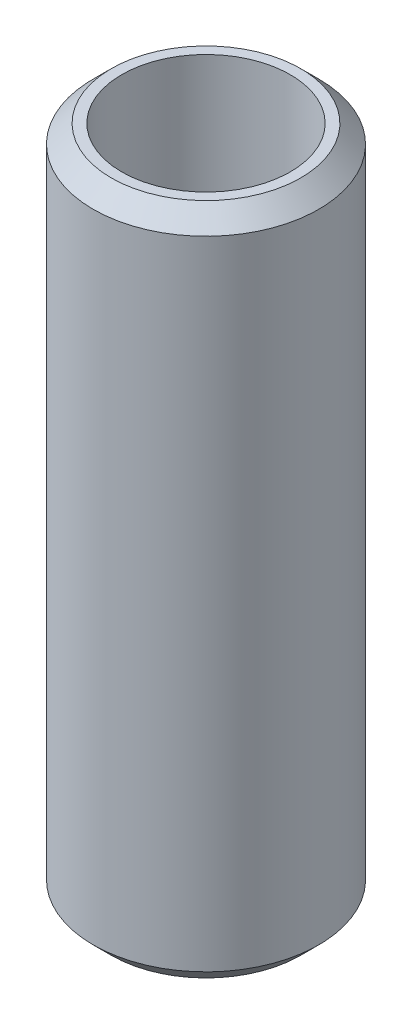
SolidWorks part; units mm, degrees
ref_plane "Front Plane" through (0, 0, 0) normal (0, 0, 1) x (1, 0, 0)
ref_plane "Top Plane" through (0, 0, 0) normal (0, 1, 0) x (1, 0, 0)
ref_plane "Right Plane" through (0, 0, 0) normal (1, 0, 0) x (0, 0, -1)
sketch "Sketch1" plane through (0, 0, 0) normal (0, 1, 0) x (1, 0, 0)
  circle A0 centre (0, 0) radius 30
  dimension "SHAFT_OD" = 60
extrude "Boss-Extrude1" add sketch "Sketch1" along normal blind 179.0214
sketch "Sketch2" plane through (0, 0, 0) normal (0, 1, 0) x (1, 0, 0)
  circle A0 centre (0, 0) radius 22.4141
  dimension "BORE_D" = 44.8282
extrude "Cut-Extrude1" cut sketch "Sketch2" along normal through all
chamfer "Chamfer1" distance 4.8129 angle 45 2 edges at (0, 179.0214, 30) (0, 0, 30)
